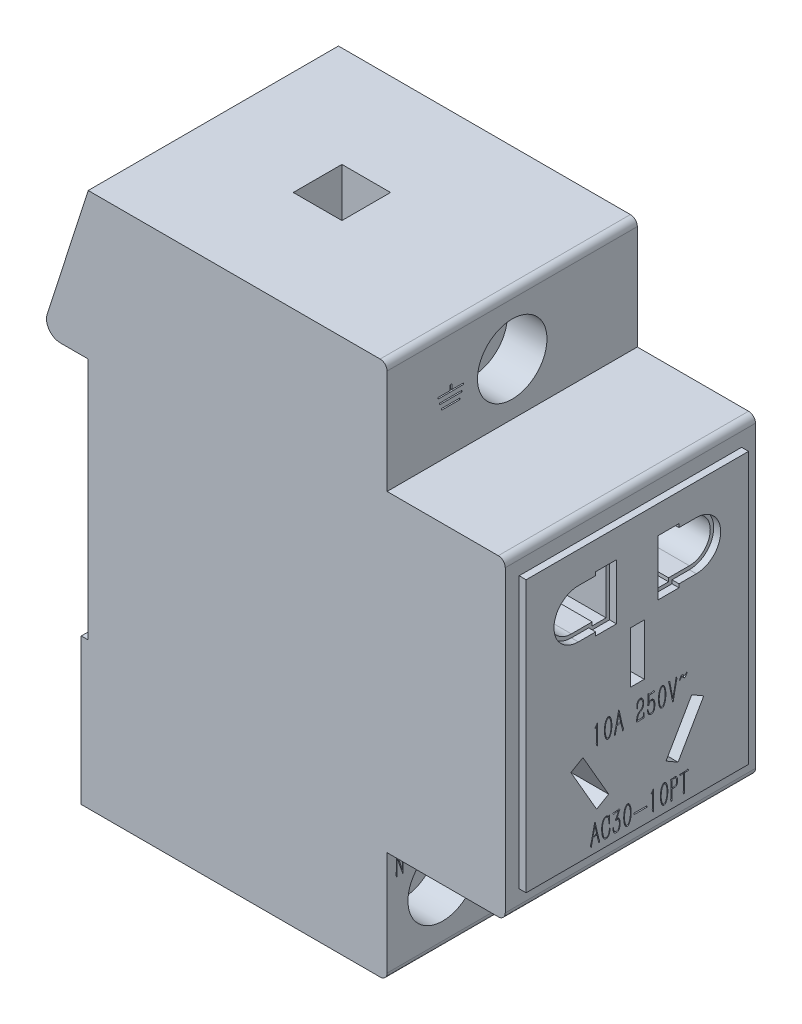
SolidWorks part; units mm, degrees
ref_plane "前视基准面" through (0, 0, 0) normal (0, 0, 1) x (1, 0, 0)
ref_plane "上视基准面" through (0, 0, 0) normal (0, 1, 0) x (1, 0, 0)
ref_plane "右视基准面" through (0, 0, 0) normal (1, 0, 0) x (0, 0, -1)
sketch "主截面" plane through (0, 0, 0) normal (0, 0, 1) x (1, 0, 0)
  line L0 (0, 1) -> (0, 20)
  line L1 (1, 21) -> (5, 21)
  line L2 (5, 21) -> (5, 56)
  line L3 (5, 56) -> (1, 56)
  line L4 (-0.9042, 58.6114) -> (5, 77)
  line L5 (5, 77) -> (47, 77)
  line L6 (48, 76) -> (48, 61)
  line L7 (48, 61) -> (64, 61)
  line L8 (65, 60) -> (65, 17)
  line L9 (64, 16) -> (48, 16)
  line L10 (48, 16) -> (48, 1)
  line L11 (47, 0) -> (1, 0)
  line L12 (65, 38.5) -> (-17.4492, 38.5) construction
  arc A0 (48, 76) -> (47, 77) centre (47, 76) ccw
  arc A1 (65, 60) -> (64, 61) centre (64, 60) ccw
  arc A2 (64, 16) -> (65, 17) centre (64, 17) ccw
  arc A3 (1, 56) -> (-0.9042, 58.6114) centre (1, 58) cw
  arc A4 (47, 0) -> (48, 1) centre (47, 1) ccw
  arc A5 (1, 0) -> (0, 1) centre (1, 1) cw
  arc A6 (1, 21) -> (0, 20) centre (1, 20) ccw
  point P16 (5, 38.5)
  point P23 (48, 77)
  point P26 (65, 61)
  point P29 (65, 16)
  point P34 (48, 0)
  point P37 (0, 0)
  point P40 (0, 21)
  dimension "D7" = 1
  dimension "D8" = 1
  dimension "D9" = 1
  dimension "D10" = 2
  dimension "D11" = 1
  dimension "D12" = 1
  dimension "D13" = 1
  dimension "D1" = 48
  dimension "D2" = 35
  dimension "D3" = 45
  dimension "D4" = 16
  dimension "D5" = 17
  dimension "D6" = 5
extrude "凸台-拉伸1" add sketch "主截面" along normal mid plane 36
sketch "草图2" plane through (5, 0, 0) normal (-1, 0, 0) x (0, 0, 1)
  line L0 (0, -1.6845) -> (0, 66.7707) construction
  line L1 (-18, 38.5) -> (18, 38.5) construction
  line L2 (-18, 56) -> (-18, 21) construction
  line L3 (18, 56) -> (18, 21) construction
  line L5 (16, 22.5001) -> (-16, 22.5001)
  line L6 (16, 22.5001) -> (16, 54.5001)
  line L7 (16, 54.5001) -> (-16, 54.5001)
  line L8 (-16, 22.5001) -> (-16, 54.5001)
  line L9 (16, 22.5001) -> (-16, 54.5001) construction
  line L10 (16, 54.5001) -> (-16, 22.5001) construction
  point P9 (0, 38.5001)
  dimension "D1" = 2
extrude "切除-拉伸1" cut sketch "草图2" against normal blind 34
sketch "草图3" plane through (48, 0, 0) normal (1, 0, 0) x (0, 0, -1)
  line L0 (0, 54.4664) -> (0, 78.831) construction
  line L1 (-18, 68.5) -> (18, 68.5) construction
  line L2 (-18, 61) -> (-18, 76) construction
  line L3 (18, 61) -> (18, 76) construction
hole_wizard "打孔尺寸(%根据)开槽圆柱头螺钉的类型1" positions "草图4" profile "草图5" counterbore size "M5" standard "GB"
sketch "草图4" plane through (48, 0, 0) normal (1, 0, 0) x (0, 0, -1)
  line L0 (-18, 68.5) -> (18, 68.5) construction
  point P0 (0, 68.5)
sketch "草图5" plane through (48, 68.5, 0) normal (0, 1, 0) x (0, 0, -1)
  line L0 (0, 0) -> (0, 9.1524)
  line L1 (0, 9.1524) -> (2.75, 7.5)
  line L2 (2.75, 7.5) -> (2.75, 5.7)
  line L3 (2.75, 5.7) -> (5, 5.7)
  line L4 (5, 5.7) -> (5, 0)
  line L5 (5, 0) -> (0, 0)
  line L10 (0, 9.1524) -> (-2.75, 7.5) construction
  line L11 (0, -6.35) -> (0, 107.95) construction
  dimension "孔直径" = 5.5
  dimension "孔深度" = 7.5
  dimension "柱形沉头孔直径" = 10
  dimension "柱形沉头孔深度" = 5.7
  dimension "导头角度" = 118
sketch "草图6" plane through (48, 0, 0) normal (1, 0, 0) x (0, 0, -1)
  line L0 (0, -2.3244) -> (0, 19.1204) construction
  line L1 (-18, 8.5) -> (18, 8.398) construction
  line L2 (-18, 1) -> (-18, 16) construction
  line L3 (18, 1) -> (18, 16) construction
  line L4 (10, 12.7282) -> (10, 4.0826) construction
  line L5 (-10, 12.7282) -> (-10, 4.0826) construction
  dimension "D1" = 8
hole_wizard "打孔尺寸(%根据)开槽圆柱头螺钉的类型3" positions "草图11" profile "草图12" counterbore size "M5" standard "GB"
sketch "草图11" plane through (48, 0, 0) normal (1, 0, 0) x (0, 0, -1)
  line L0 (10, 12.7282) -> (10, 4.0826) construction
  line L1 (-18, 8.5) -> (18, 8.398) construction
  point P0 (10, 8.4054)
  point P4 (-10.0035, 8.4773)
sketch "草图12" plane through (48, 8.4054, -10) normal (0, 1, 0) x (0, 0, -1)
  line L0 (0, 0) -> (0, 9.1524)
  line L1 (0, 9.1524) -> (2.75, 7.5)
  line L2 (2.75, 7.5) -> (2.75, 5.7)
  line L3 (2.75, 5.7) -> (5, 5.7)
  line L4 (5, 5.7) -> (5, 0)
  line L5 (5, 0) -> (0, 0)
  line L10 (0, 9.1524) -> (-2.75, 7.5) construction
  line L11 (0, -6.35) -> (0, 107.95) construction
  dimension "孔直径" = 5.5
  dimension "孔深度" = 7.5
  dimension "柱形沉头孔直径" = 10
  dimension "柱形沉头孔深度" = 5.7
  dimension "导头角度" = 118
sketch "草图13" plane through (65, 0, 0) normal (1, 0, 0) x (0, 0, -1)
  line L0 (0, 54.4664) -> (0, 17.3083) construction
  line L1 (0, -2.3244) -> (0, 19.1204) construction
  line L2 (-18, 38.5) -> (18, 38.5) construction
  line L3 (-18, 17) -> (-18, 60) construction
  line L4 (18, 17) -> (18, 60) construction
  line L5 (-18, 60) -> (18, 60) construction
  line L6 (-16, 58) -> (16, 58)
  line L7 (-16, 58) -> (-16, 19)
  line L8 (-16, 19) -> (16, 19)
  line L9 (16, 58) -> (16, 19)
  line L10 (-16, 58) -> (16, 19) construction
  line L11 (-16, 19) -> (16, 58) construction
  point P11 (0, 38.5)
  dimension "D1" = 2
  dimension "D2" = 2
extrude "凸台-拉伸2" add sketch "草图13" along normal blind 1
sketch "3P插孔" plane through (66, 0, 0) normal (1, 0, 0) x (0, 0, -1)
  line L0 (0, 56.3164) -> (0, 19.8814) construction
  line L1 (0, 54.4664) -> (0, 78.831) construction
  line L2 (-16, 32) -> (16, 32) construction
  line L5 (0, 32) -> (-16.773, 22.3161) construction
  line L6 (0, 32) -> (16.0259, 22.7474) construction
  line L7 (4.1256, 25.3457) -> (5.8576, 24.3457)
  line L8 (-4.1256, 25.3457) -> (-5.8576, 24.3457)
  line L9 (-4.1256, 25.3457) -> (-7.8256, 31.7543)
  line L10 (-7.8256, 31.7543) -> (-9.5576, 30.7543)
  line L11 (-5.8576, 24.3457) -> (-9.5576, 30.7543)
  line L12 (-4.1256, 25.3457) -> (-9.5576, 30.7543) construction
  line L13 (-7.8256, 31.7543) -> (-5.8576, 24.3457) construction
  line L14 (5.8576, 24.3457) -> (9.5576, 30.7543)
  line L15 (7.8256, 31.7543) -> (9.5576, 30.7543)
  line L16 (4.1256, 25.3457) -> (7.8256, 31.7543)
  line L17 (-16, 19) -> (16, 19) construction
  line L18 (-1, 37.1) -> (1, 37.1)
  line L19 (-1, 37.1) -> (-1, 44.5)
  line L20 (-1, 44.5) -> (1, 44.5)
  line L21 (1, 37.1) -> (1, 44.5)
  line L22 (-1, 37.1) -> (1, 44.5) construction
  line L23 (-1, 44.5) -> (1, 37.1) construction
  point P17 (-6.8416, 28.05)
  point P24 (0, 40.8)
  dimension "D1" = 120
  dimension "D2" = 120
  dimension "D3" = 7.9
  dimension "D4" = 7.4
  dimension "D5" = 2
  dimension "D6" = 8.8
  dimension "D7" = 13
extrude "切除-拉伸2" cut sketch "3P插孔" against normal blind 12
sketch "草图15" plane through (0, 77, 0) normal (0, 1, 0) x (1, 0, 0)
  line L0 (27, 17.564) -> (27, -11.7203) construction
  line L1 (47, -18) -> (47, 18) construction
  line L2 (1.6728, 0) -> (46.6497, 0) construction
  line L4 (20, 3.5) -> (27, 3.5)
  line L5 (20, 3.5) -> (20, -3.5)
  line L6 (20, -3.5) -> (27, -3.5)
  line L7 (27, 3.5) -> (27, -3.5)
  line L8 (20, 3.5) -> (27, -3.5) construction
  line L9 (20, -3.5) -> (27, 3.5) construction
  point P7 (23.5, 0)
  dimension "D1" = 20
  dimension "D2" = 7
extrude "切除-拉伸3" cut sketch "草图15" against normal blind 12
sketch "草图16" plane through (0, 0, 0) normal (0, -1, 0) x (1, 0, 0)
  line L0 (-1.4132, 0) -> (48.521, 0) construction
  line L1 (28, 18.5489) -> (28, -18.6474) construction
  line L3 (48, 18) -> (48, -18) construction
  line L4 (28, 12.5) -> (28, 5.5)
  line L5 (28, -12.5) -> (21, -12.5)
  line L6 (28, -12.5) -> (28, -5.5)
  line L7 (28, -5.5) -> (21, -5.5)
  line L8 (21, -12.5) -> (21, -5.5)
  line L9 (28, -12.5) -> (21, -5.5) construction
  line L10 (28, -5.5) -> (21, -12.5) construction
  line L11 (28, 12.5) -> (21, 12.5)
  line L12 (21, 12.5) -> (21, 5.5)
  line L13 (28, 5.5) -> (21, 5.5)
  point P7 (24.5, -9)
  dimension "D1" = 20
  dimension "D2" = 7
  dimension "D3" = 11
extrude "切除-拉伸4" cut sketch "草图16" against normal blind 12
sketch "草图17" plane through (0, 0, 0) normal (0, -1, 0) x (1, 0, 0)
  line L0 (-3.8098, 0) -> (13.4587, 0) construction
  line L1 (4, 19.7636) -> (4, -19.9323) construction
  line L2 (-1, 18) -> (-1, -18) construction
  line L3 (1, -18) -> (47, -18) construction
  line L4 (4, -9) -> (-1, -9)
  line L5 (4, -9) -> (4, -19.9323)
  line L6 (4, -19.9323) -> (-1, -19.9323)
  line L7 (-1, -9) -> (-1, -19.9323)
  line L8 (-1, 9) -> (-1, 19.9323)
  line L9 (4, 19.9323) -> (-1, 19.9323)
  line L10 (4, 9) -> (4, 19.9323)
  line L11 (4, 9) -> (-1, 9)
  line L13 (4, 6.9928) -> (-1, 6.9928)
  line L14 (4, 6.9928) -> (4, -6.9928)
  line L15 (4, -6.9928) -> (-1, -6.9928)
  line L16 (-1, 6.9928) -> (-1, -6.9928)
  line L17 (4, 6.9928) -> (-1, -6.9928) construction
  line L18 (4, -6.9928) -> (-1, 6.9928) construction
  point P16 (1.5, 0)
  dimension "D1" = 5
  dimension "D2" = 9
extrude "切除-拉伸5" cut sketch "草图17" against normal up to surface (21 mm away) up to face at (3, 21, 0)
sketch "文字NL" plane through (48, 0, 0) normal (1, 0, 0) x (0, 0, -1)
  text T0 "N                    L" font "汉仪长仿宋体" height 3
extrude "切除-拉伸8" cut sketch "文字NL" against normal blind 0.25
sketch "接地符号" plane through (48, 0, 0) normal (1, 0, 0) x (0, 0, -1)
  text T0 "⏚" font "新宋体" height 3.5
extrude "切除-拉伸9" cut sketch "接地符号" against normal blind 0.25
sketch "2P插孔" plane through (66, 0, 0) normal (1, 0, 0) x (0, 0, -1)
  line L0 (8.4921, 53) -> (5.4921, 53)
  line L1 (-14.5329, 50) -> (14.5329, 50) construction
  line L2 (16, 58) -> (-16, 58) construction
  line L3 (0, 56.1674) -> (0, 23.1674) construction
  line L4 (-7, 50) -> (7, 50) construction
  line L10 (5.4921, 53) -> (5.4921, 53.5)
  line L11 (5.4921, 53.5) -> (3.4921, 53.5)
  line L14 (-8.4921, 47) -> (-5.4921, 47)
  line L15 (-5.4921, 46.5) -> (-5.4921, 47)
  line L16 (-5.4921, 46.5) -> (-3.4921, 46.5)
  line L17 (-3.4921, 46.5) -> (-3.4921, 53.5)
  line L18 (-5.4921, 53.5) -> (-3.4921, 53.5)
  line L19 (-5.4921, 53) -> (-5.4921, 53.5)
  line L20 (-8.4921, 53) -> (-5.4921, 53)
  line L22 (-5.4921, 47) -> (-5.4921, 46.5)
  line L29 (-8.4921, 47) -> (-5.4921, 47)
  line L30 (-5.4921, 46.5) -> (-3.4921, 46.5)
  line L31 (-3.4921, 53.5) -> (-3.4921, 46.5)
  line L32 (-5.4921, 53.5) -> (-3.4921, 53.5)
  line L33 (-5.4921, 53.5) -> (-5.4921, 53)
  line L34 (-8.4921, 53) -> (-5.4921, 53)
  line L35 (3.4921, 46.5) -> (3.4921, 53.5)
  line L36 (5.4921, 46.5) -> (3.4921, 46.5)
  line L37 (5.4921, 46.5) -> (5.4921, 47)
  line L38 (8.4921, 47) -> (5.4921, 47)
  line L39 (-2.9921, 46) -> (-2.9921, 54)
  line L40 (-5.9921, 54) -> (-2.9921, 54)
  line L41 (-5.9921, 53.5) -> (-5.9921, 54)
  line L42 (-8.4921, 53.5) -> (-5.9921, 53.5)
  line L43 (-8.4921, 46.5) -> (-5.9921, 46.5)
  line L44 (-5.9921, 46) -> (-5.9921, 46.5)
  line L45 (-5.9921, 46) -> (-2.9921, 46)
  line L46 (8.4921, 46.5) -> (5.9921, 46.5)
  line L47 (5.9921, 46) -> (5.9921, 46.5)
  line L48 (5.9921, 46) -> (2.9921, 46)
  line L49 (2.9921, 46) -> (2.9921, 54)
  line L50 (5.9921, 54) -> (2.9921, 54)
  line L51 (5.9921, 53.5) -> (5.9921, 54)
  line L52 (8.4921, 53.5) -> (5.9921, 53.5)
  arc A1 (-8.4921, 53) -> (-8.4921, 47) centre (-8.4921, 50) ccw
  arc A3 (-8.4921, 47) -> (-8.4921, 53) centre (-8.4921, 50) cw
  arc A4 (8.4921, 53) -> (8.4921, 47) centre (8.4921, 50) cw
  arc A5 (-8.4921, 53.5) -> (-8.4921, 46.5) centre (-8.4921, 50) ccw
  arc A6 (8.4921, 53.5) -> (8.4921, 46.5) centre (8.4921, 50) cw
  point P11 (0, 44.1595)
  dimension "D1" = 8
  dimension "D2" = 0.5
  dimension "D3" = 0.5
extrude "切除-拉伸10" cut sketch "2P插孔" against normal blind 1 contours L40 L39 L45 L44 L43 A5 L42 L41 | L50 L49 L48 L47 L46 A6 L52 L51
extrude "切除-拉伸11" cut sketch "2P插孔<4>" against normal blind 10 contours L14 L15 L16 L17 L18 L19 L20 A1 | L36 L35 L11 L10 L0 A4 L38 L37
sketch "2P插孔<4>" plane through (66, 0, 0) normal (1, 0, 0) x (0, 0, -1) same geometry as "2P插孔"
sketch "文字10A250V" plane through (66, 0, 0) normal (1, 0, 0) x (0, 0, -1)
  text T0 "10A 250V~" font "汉仪长仿宋体" height 3
extrude "切除-拉伸12" cut sketch "文字10A250V" against normal blind 0.25
sketch "文字AC30-10PT" plane through (66, 0, 0) normal (1, 0, 0) x (0, 0, -1)
  text T0 "AC30-10PT" font "汉仪长仿宋体" height 3
extrude "切除-拉伸13" cut sketch "文字AC30-10PT" against normal blind 0.25
